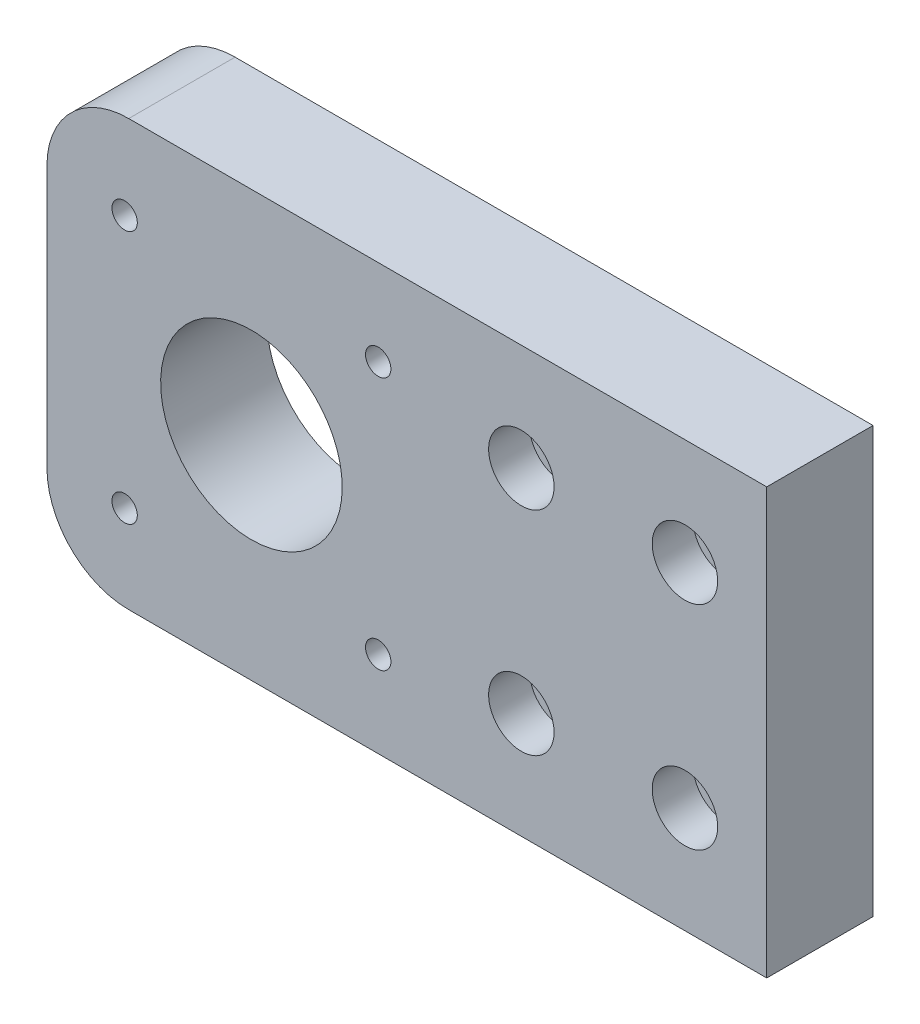
SolidWorks part; units mm, degrees
ref_plane "Alzado" through (0, 0, 0) normal (0, 0, 1) x (1, 0, 0)
ref_plane "Planta" through (0, 0, 0) normal (0, 1, 0) x (1, 0, 0)
ref_plane "Vista lateral" through (0, 0, 0) normal (1, 0, 0) x (0, 0, -1)
sketch "Croquis1" plane through (0, 0, 0) normal (0, 0, 1) x (1, 0, 0)
  line L0 (10, -240) -> (10, 0) construction
  line L1 (10, -26) -> (-78, -26)
  line L2 (10, -26) -> (10, -78)
  line L3 (10, -78) -> (-78, -78)
  line L4 (-78, -26) -> (-78, -78)
  line L5 (-53, -52) -> (-78, -52) construction
  circle A0 centre (-53, -52) radius 11 construction
  circle A1 centre (-53, -52) radius 11 construction
  circle A2 centre (-53, -52) radius 11.1
  dimension "D3" = 22.2
  dimension "D1" = 52
  dimension "D2" = 88
extrude "Saliente-Extruir1" add sketch "Croquis1" along normal blind 13
sketch "Croquis2" plane through (0, 0, 13) normal (0, 0, 1) x (1, 0, 0)
  line L0 (10, -52) -> (-78, -52) construction
  line L1 (10, -78) -> (10, -26) construction
  line L2 (-78, -26) -> (-78, -78) construction
  circle A0 centre (-68.5, -36.5) radius 1.55
  circle A1 centre (-37.5, -36.5) radius 1.55
  circle A2 centre (-37.5, -67.5) radius 1.55
  circle A3 centre (-68.5, -67.5) radius 1.55
  circle A4 centre (-20, -65) radius 2.05
  circle A5 centre (0, -65) radius 2.05
  circle A6 centre (0, -39) radius 2.05
  circle A7 centre (-20, -39) radius 2.05
  dimension "D1" = 3.1
  dimension "D2" = 4.1
  dimension "D3" = 10
  dimension "D4" = 20
  dimension "D5" = 13
extrude "Cortar-Extruir1" cut sketch "Croquis2" against normal up to next
sketch "Croquis3" plane through (0, 0, 13) normal (0, 0, 1) x (1, 0, 0)
  circle A0 centre (-20, -39) radius 4
  circle A1 centre (0, -39) radius 4
  circle A2 centre (0, -65) radius 4
  circle A3 centre (-20, -65) radius 4
  dimension "D1" = 8
extrude "Cortar-Extruir2" cut sketch "Croquis3" against normal blind 5
fillet "Redondeo1" radius 10 2 edges at (-78, -78, 6.5) (-78, -26, 6.5)
sketch "Croquis4" plane through (0, 0, 0) normal (0, 0, -1) x (-1, 0, 0)
  circle A0 centre (37.5, -36.5) radius 3.25
  circle A1 centre (68.5, -36.5) radius 3.25
  circle A2 centre (68.5, -67.5) radius 3.25
  circle A3 centre (37.5, -67.5) radius 3.25
  dimension "D1" = 6.5
extrude "Cortar-Extruir3" cut sketch "Croquis4" against normal blind 5
sketch "Croquis5" plane through (0, 0, 0) normal (0, 0, -1) x (-1, 0, 0)
  line L0 (30, -240) -> (30, 0) construction
  line L1 (30, -43.25) -> (39.5, -43.25)
  line L2 (30, -43.25) -> (30, -60.75)
  line L3 (30, -60.75) -> (39.5, -60.75)
  line L4 (39.5, -43.25) -> (39.5, -60.75)
  line L5 (30, -52) -> (53, -52) construction
  dimension "D1" = 9.5
  dimension "D2" = 17.5
extrude "Saliente-Extruir2" add sketch "Croquis5" along normal blind 20
fillet "Redondeo2" radius 10 1 edges at (-39.5, -52, 0)
sketch "Croquis6" plane through (-39.5, 0, 0) normal (-1, 0, 0) x (0, 0, 1)
  line L1 (-20, -60.75) -> (-20, -43.25) construction
  line L2 (-10, -52) -> (0, -52) construction
  line L3 (0, -36) -> (0, -68) construction
  circle A0 centre (-10, -52) radius 2.05
  dimension "D2" = 4.1
  dimension "D3" = 10
extrude "Cortar-Extruir4" cut sketch "Croquis6" against normal up to next
sketch "Croquis7" plane through (-39.5, 0, 0) normal (-1, 0, 0) x (0, 0, 1)
  circle A0 centre (-10, -52) radius 4
  dimension "D1" = 8
extrude "Cortar-Extruir5" cut sketch "Croquis7" against normal blind 4 and the other way up to next
fillet "Redondeo3" radius 5 2 edges at (-34.75, -60.75, -20) (-34.75, -43.25, -20)
